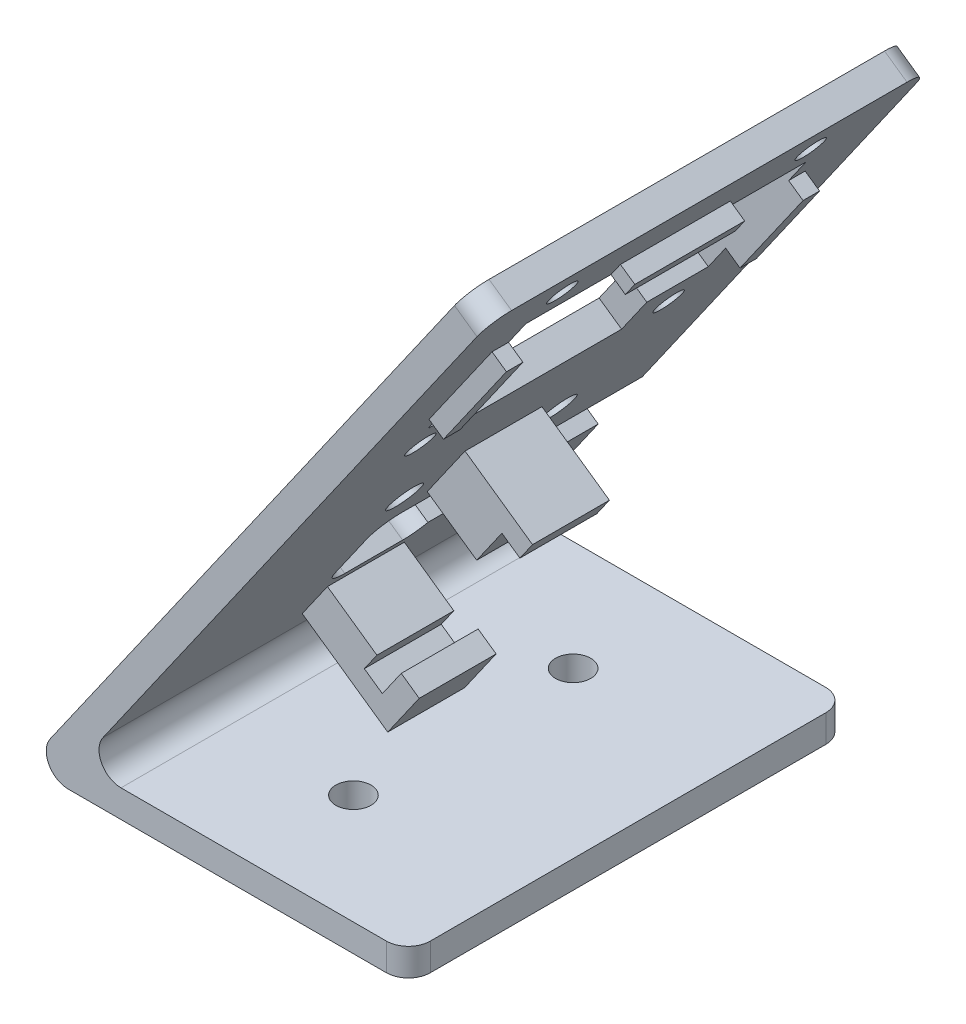
SolidWorks part; units mm, degrees
ref_plane "Front Plane" through (0, 0, 0) normal (0, 0, 1) x (1, 0, 0)
ref_plane "Top Plane" through (0, 0, 0) normal (0, 1, 0) x (1, 0, 0)
ref_plane "Right Plane" through (0, 0, 0) normal (1, 0, 0) x (0, 0, -1)
sketch "Sketch1" plane through (0, 0, 0) normal (0, 0, 1) x (1, 0, 0)
  line L0 (0, 0) -> (37.3958, 53.4067)
  line L1 (0, 0) -> (30, 0)
  line L3 (0, -2.5) -> (30, -2.5)
  line L4 (30, 0) -> (30, -2.5)
  line L5 (37.3958, 53.4067) -> (35.3479, 54.8406)
  line L6 (35.3479, 54.8406) -> (-4.8025, -2.5)
  line L7 (0, -2.5) -> (-4.8025, -2.5)
  dimension "D5" = 70
  dimension "D1" = 2.5
  dimension "D2" = 30
  dimension "D3" = 55
  dimension "D4" = 2.5
extrude "Boss-Extrude1" add sketch "Sketch1" along normal blind 40
sketch "Sketch2" plane through (-2.0479, 1.4339, 0) normal (-0.8192, 0.5736, 0) x (0, 0, 1)
  line L0 (20, 65.1975) -> (20, -4.8025) construction
  line L1 (40, 65.1975) -> (0, 65.1975) construction
  line L2 (40, -4.8025) -> (0, -4.8025) construction
  line L5 (32.75, 42.8125) -> (32.75, 58.3125)
  line L6 (32.75, 58.3125) -> (7.25, 58.3125)
  line L7 (7.25, 42.8125) -> (7.25, 58.3125)
  line L9 (10.8, 25.1975) -> (24.8, 25.1975) construction
  line L14 (12.85, 42.8125) -> (12.85, 38.8125)
  line L15 (26.85, 42.8125) -> (26.85, 38.8125)
  line L22 (15.5, 20.6975) -> (24.5, 20.6975)
  line L23 (15.5, 20.6975) -> (15.5, 11.6975)
  line L24 (15.5, 11.6975) -> (24.5, 11.6975)
  line L25 (24.5, 20.6975) -> (24.5, 11.6975)
  line L26 (12.85, 38.8125) -> (26.85, 38.8125)
  line L34 (12.85, 42.8125) -> (7.25, 42.8125)
  line L38 (26.85, 42.8125) -> (32.75, 42.8125)
  line L42 (0, 65.1975) -> (0, -4.8025) construction
  line L43 (0, 19.6975) -> (15.5, 19.6975)
  line L44 (0, 19.6975) -> (0, 12.6975)
  line L45 (0, 12.6975) -> (15.5, 12.6975)
  line L46 (15.5, 19.6975) -> (15.5, 12.6975)
  circle A0 centre (8.7, 61.5775) radius 1.25
  circle A1 centre (31.3, 61.5775) radius 1.25
  circle A2 centre (31.3, 39.0475) radius 1.25
  circle A3 centre (8.7, 39.0475) radius 1.25
  circle A4 centre (24.8, 25.1975) radius 1.5
  circle A5 centre (10.8, 25.1975) radius 1.5
  point P8 (15.5, 16.1975)
  point P12 (7.25, 50.5625)
  point P13 (24.5, 16.1975)
  point P14 (20, 58.3125)
  point P53 (20, 20.6975)
  dimension "D6" = 2.5
  dimension "D16" = 3
  dimension "D17" = 3
  dimension "D27" = 2.5
  dimension "D28" = 2.5
  dimension "D29" = 2.5
  dimension "D3" = 21
  dimension "D4" = 14
  dimension "D5" = 9
  dimension "D7" = 4.7
  dimension "D8" = 15.5
  dimension "D11" = 15.5
  dimension "D12" = 25.5
  dimension "D13" = 5.6
  dimension "D14" = 9
  dimension "D15" = 9
  dimension "D18" = 4
  dimension "D19" = 14.635
  dimension "D20" = 3.265
  dimension "D21" = 1.45
  dimension "D22" = 1.45
  dimension "D23" = 14
  dimension "D24" = 1.45
  dimension "D25" = 3.765
  dimension "D26" = 1.45
  dimension "D9" = 3.265
  dimension "D10" = 3.765
  dimension "D30" = 7
extrude "Cut-Extrude2" cut sketch "Sketch2" against normal blind 5
sketch "Sketch4" plane through (0, 0, 0) normal (0.8192, -0.5736, 0) x (0, 0, -1)
  line L0 (-20, 11.6975) -> (-20, 10.6975) construction
  line L10 (-15.5, 20.6975) -> (-24.5, 20.6975) construction
  line L12 (-21.3, 22.6975) -> (-14.3, 22.6975)
  line L13 (-21.3, 22.6975) -> (-21.3, 26.6975)
  line L14 (-21.3, 26.6975) -> (-14.3, 26.6975)
  line L15 (-14.3, 22.6975) -> (-14.3, 26.6975)
  line L16 (-20, 20.6975) -> (-20, 22.6975) construction
  line L17 (-23.5, 10.6975) -> (-16.5, 10.6975)
  line L18 (-23.5, 10.6975) -> (-23.5, 8.6975)
  line L19 (-23.5, 8.6975) -> (-16.5, 8.6975)
  line L20 (-16.5, 10.6975) -> (-16.5, 8.6975)
  line L21 (-15.5, 11.6975) -> (-24.5, 11.6975) construction
  point P17 (-20, 10.6975)
  dimension "D1" = 7
  dimension "D2" = 2
  dimension "D3" = 2
  dimension "D4" = 4
  dimension "D5" = 7
  dimension "D6" = 1
  dimension "D7" = 1.3
extrude "Boss-Extrude2" add sketch "Sketch4" along normal blind 5.5
sketch "Sketch6" plane through (0, 0, 0) normal (0.8192, -0.5736, 0) x (0, 0, -1)
  line L9 (-14.3, 26.6975) -> (-21.3, 26.6975)
  line L10 (-14.3, 26.6975) -> (-14.3, 28.6975)
  line L11 (-14.3, 28.6975) -> (-21.3, 28.6975)
  line L12 (-21.3, 26.6975) -> (-21.3, 28.6975)
  line L13 (-16.5, 8.6975) -> (-23.5, 8.6975)
  line L14 (-16.5, 8.6975) -> (-16.5, 6.6975)
  line L15 (-16.5, 6.6975) -> (-23.5, 6.6975)
  line L16 (-23.5, 8.6975) -> (-23.5, 6.6975)
  dimension "D1" = 2
  dimension "D2" = 2
extrude "Boss-Extrude3" add sketch "Sketch6" along normal offset from surface (7.5 mm away) 2 up to face at (18.6713, 17.0764, 17.8) offset beyond the face yes
sketch "Sketch8" plane through (4.9887, 7.1246, 21.1975) normal (0.5736, 0.8192, 0) x (0.671, -0.4698, -0.5736)
  line L2 (8.838, -0.4538) -> (4.823, -6.1879)
  line L4 (4.823, -6.1879) -> (6.4613, -7.335)
  line L10 (6.4613, -7.335) -> (10.4763, -1.601)
  line L11 (10.4763, -1.601) -> (8.838, -0.4538)
  dimension "D1" = 2
extrude "Boss-Extrude4" add sketch "Sketch8" along normal blind 3 and the other way up to surface (2 mm away) other way up to face at (6.9134, 3.3354, 20)
sketch "Sketch10" plane through (0, 0, 0) normal (0.8192, -0.5736, 0) x (0, 0, -1)
  line L0 (-32.75, 42.8125) -> (-32.75, 58.3125) construction
  line L1 (-32.75, 55.5625) -> (-34.25, 55.5625)
  line L2 (-32.75, 55.5625) -> (-32.75, 45.5625)
  line L3 (-32.75, 45.5625) -> (-34.25, 45.5625)
  line L4 (-34.25, 55.5625) -> (-34.25, 45.5625)
  line L5 (-7.25, 42.8125) -> (-7.25, 58.3125) construction
  line L6 (-7.25, 55.5625) -> (-5.75, 55.5625)
  line L7 (-7.25, 55.5625) -> (-7.25, 45.5625)
  line L8 (-7.25, 45.5625) -> (-5.75, 45.5625)
  line L9 (-5.75, 55.5625) -> (-5.75, 45.5625)
  line L10 (-32.75, 58.3125) -> (-7.25, 58.3125) construction
  line L11 (-25, 58.3125) -> (-15, 58.3125)
  line L12 (-25, 58.3125) -> (-25, 59.8125)
  line L13 (-25, 59.8125) -> (-15, 59.8125)
  line L14 (-15, 58.3125) -> (-15, 59.8125)
  point P7 (-32.75, 50.5625)
  point P13 (-7.25, 50.5625)
  point P20 (-20, 58.3125)
  dimension "D1" = 1.5
  dimension "D2" = 10
  dimension "D3" = 1.5
  dimension "D4" = 10
  dimension "D5" = 10
  dimension "D6" = 1.5
extrude "Boss-Extrude6" add sketch "Sketch10" along normal blind 1.6
sketch "Sketch5" plane through (0, 0, 0) normal (0, 1, 0) x (1, 0, 0)
  line L0 (15, 0) -> (15, -40) construction
  line L1 (30, 0) -> (0, 0) construction
  line L2 (30, -40) -> (0, -40) construction
  circle A0 centre (15, -10) radius 1.6
  circle A1 centre (15, -30) radius 1.6
  point P8 (15, -20)
  dimension "D1" = 10
  dimension "D2" = 3.2
  dimension "D3" = 10
  dimension "D4" = 3.2
extrude "Cut-Extrude3" cut sketch "Sketch5" against normal blind 10
fillet "Fillet1" radius 2 14 edges at (36.3718, 54.1237, 40) (-4.8025, -2.5, 20) (0, 0, 20) (30, -1.25, 40) (10.8477, 17.6714, 24.5) (5.6855, 10.299, 24.5) (6.9962, 9.9916, 15.5) (5.6855, 10.299, 15.5) (11.5848, 16.5449, 15.5) (10.8477, 17.6714, 15.5) (9.537, 17.9788, 15.5) (4.9483, 11.4256, 15.5) (30, -1.25, 0) (36.3718, 54.1237, 0)
